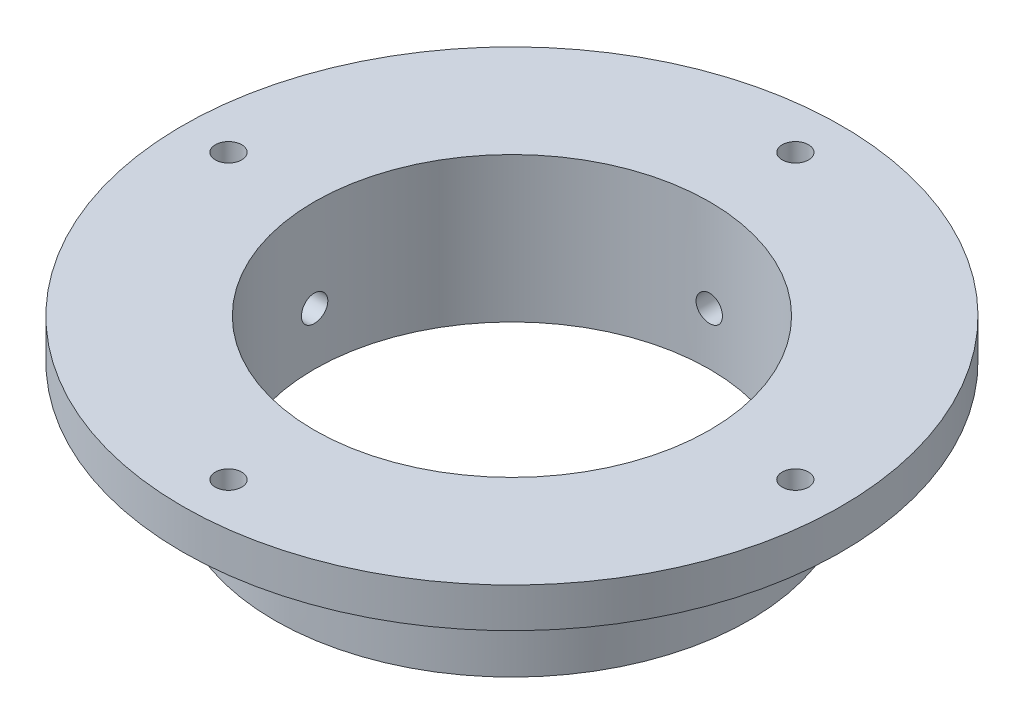
SolidWorks part; units mm, degrees
ref_plane "Front Plane" through (0, 0, 0) normal (0, 0, 1) x (1, 0, 0)
ref_plane "Top Plane" through (0, 0, 0) normal (0, 1, 0) x (1, 0, 0)
ref_plane "Right Plane" through (0, 0, 0) normal (1, 0, 0) x (0, 0, -1)
sketch "Sketch1" plane through (0, 0, 0) normal (0, 0, 1) x (1, 0, 0)
  line L0 (-15, -10) -> (-15, -18)
  line L1 (-15, -18) -> (0, -18)
  line L2 (-18, -13) -> (-18, -21)
  line L3 (-18, -21) -> (0, -21)
  line L4 (-25, -10) -> (-15, -10)
  line L5 (-25, -13) -> (-18, -13)
  line L6 (-25, -10) -> (-25, -13)
  line L7 (15, -10) -> (18, -10)
  line L8 (0, 0) -> (0, -21) construction
  line L9 (0, -21) -> (0, -18)
  line L10 (-15, -18) -> (-15, -27.5757)
sketch "Sketch2" plane through (0, 0, 0) normal (0, 0, 1) x (1, 0, 0)
  line L2 (-25, -10) -> (-25, -13) construction
  line L3 (-15, -10) -> (-15, -18) construction
  line L4 (-25, -10) -> (-15, -10) construction
  line L5 (-25, -13) -> (-18, -13) construction
  line L6 (-18, -13) -> (-18, -21) construction
  line L7 (-18, -21) -> (0, -21) construction
  line L12 (-25, -10) -> (-25, -13)
  line L13 (-15, -10) -> (-15, -21)
  line L14 (-25, -10) -> (-15, -10)
  line L15 (-25, -13) -> (-18, -13)
  line L16 (-18, -13) -> (-18, -21)
  line L17 (-18, -21) -> (-15, -21)
  line L19 (0, 0) -> (0, -21) construction
  line L20 (0, 0) -> (0, -21)
revolve "Revolve1" add sketch "Sketch2" angle 360 about L20 region at (-20, -10.1487, 0)
sketch "Sketch3" plane through (0, -13, 0) normal (0, -1, 0) x (1, 0, 0)
  line L0 (-18, 0) -> (-25, 0) construction
  line L1 (-25, 0) -> (-18, 0) construction
  line L2 (-25, 0) -> (-15, 0) construction
  circle A0 centre (0, 21.5) radius 3
  circle A1 centre (0, 0) radius 21.5 construction
  circle A2 centre (0, 0) radius 18 construction
  circle A3 centre (0, 0) radius 25 construction
  point P15 (-21.5, 0)
  dimension "D1" = 6
extrude "Cut-Extrude1" cut sketch "Sketch3" against normal blind 0.5
pattern_circular "CirPattern1" count 4 over 360 about axis through (0, -21, 0) along (0, 1, 0) of "Cut-Extrude1"
sketch "Sketch4" plane through (0, -12.5, 0) normal (0, -1, 0) x (1, 0, 0)
  circle A0 centre (0, 21.5) radius 1
  dimension "D1" = 2
extrude "Cut-Extrude2" cut sketch "Sketch4" against normal through all both and the other way through all
pattern_circular "CirPattern2" count 4 over 360 about axis through (0, -21, 0) along (0, 1, 0) of "Cut-Extrude2"
sketch "Sketch5" plane through (0, 0, 0) normal (1, 0, 0) x (0, 0, -1)
  line L0 (0, -13) -> (0, -21) construction
  circle A0 centre (0, -17) radius 1
  dimension "D1" = 2
extrude "Cut-Extrude3" cut sketch "Sketch5" against normal through all both and the other way through all
pattern_circular "CirPattern3" count 4 over 360 about axis through (0, -21, 0) along (0, 1, 0) of "Cut-Extrude3"
fillet "Fillet1" radius 1 1 edges at (0, -13, 18)
